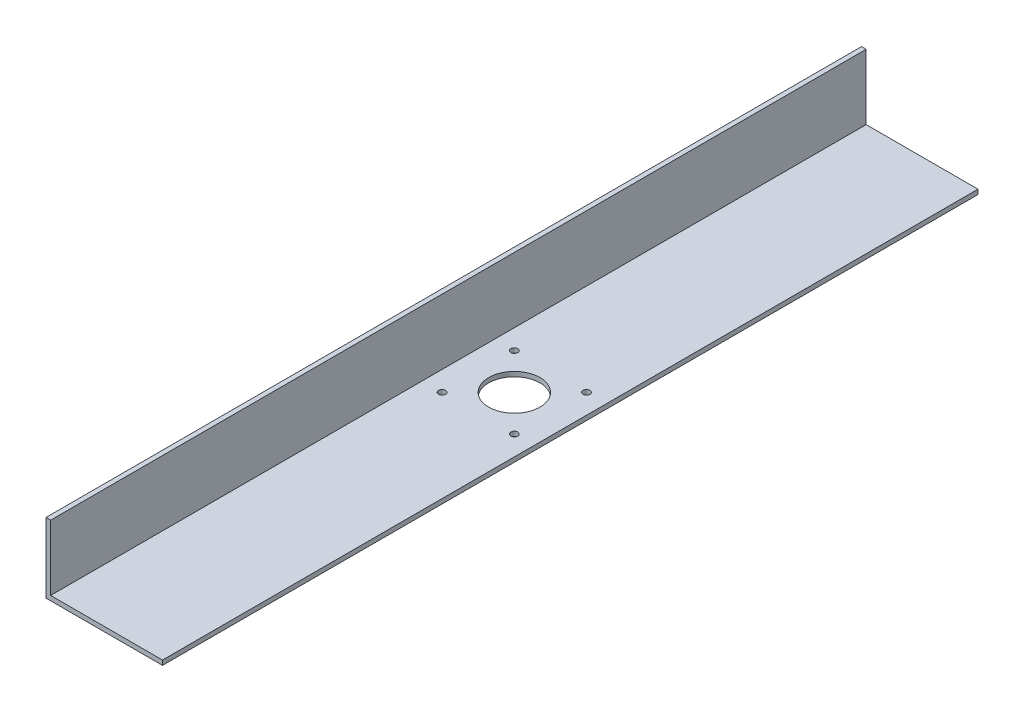
SolidWorks part; units mm, degrees
ref_plane "Front Plane" through (0, 0, 0) normal (0, 0, 1) x (1, 0, 0)
ref_plane "Top Plane" through (0, 0, 0) normal (0, 1, 0) x (1, 0, 0)
ref_plane "Right Plane" through (0, 0, 0) normal (1, 0, 0) x (0, 0, -1)
sketch "Sketch1" plane through (0, 0, 0) normal (0, 0, 1) x (1, 0, 0)
  line L0 (0, 0) -> (0, 30)
  line L1 (0, 30) -> (2, 30)
  line L2 (2, 30) -> (2, 2)
  line L3 (2, 2) -> (50, 2)
  line L4 (50, 2) -> (50, 0)
  line L5 (50, 0) -> (0, 0)
extrude "Boss-Extrude1" add sketch "Sketch1" along normal up to surface (350 mm away)
sketch "Sketch7" plane through (0, 2, 0) normal (0, 1, 0) x (1, 0, 0)
  circle A0 centre (26, -175) radius 11
  point P7 (2, -350)
extrude "Cut-Extrude1" cut sketch "Sketch7" against normal through all from surface starting at face at (26, 2, 175)
sketch "Sketch8" plane through (0, 2, 0) normal (0, 1, 0) x (1, 0, 0)
  circle A0 centre (41.5, -190.5) radius 1.5
  circle A1 centre (41.5, -159.5) radius 1.5
  circle A2 centre (10.5, -190.5) radius 1.5
  circle A3 centre (10.5, -159.5) radius 1.5
extrude "Cut-Extrude2" cut sketch "Sketch8" against normal through all
